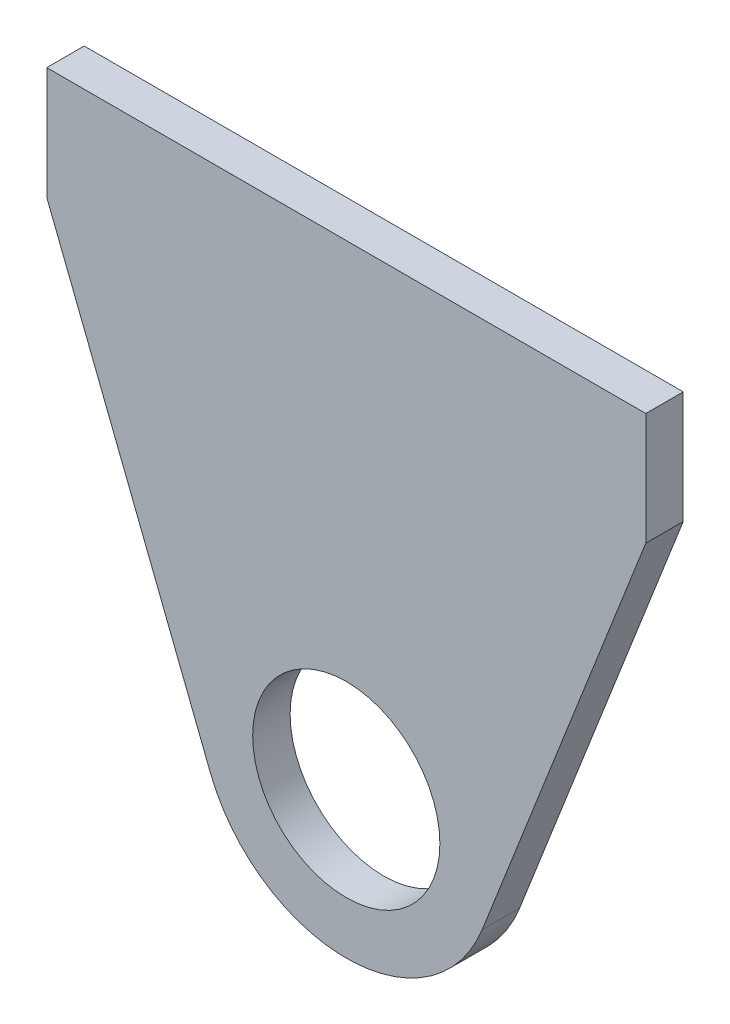
SolidWorks part; units mm, degrees
material "AISI 1020"
ref_plane "Спереди" through (0, 0, 0) normal (0, 0, 1) x (1, 0, 0)
ref_plane "Сверху" through (0, 0, 0) normal (0, 1, 0) x (1, 0, 0)
ref_plane "Справа" through (0, 0, 0) normal (1, 0, 0) x (0, 0, -1)
sketch "Эскиз2" plane through (0, 0, 0) normal (0, 0, 1) x (1, 0, 0)
  line L0 (0, -1065) -> (0, 48935) construction
  line L1 (-18.1501, -72.129) -> (-40, -16.5)
  line L2 (18.1501, -72.129) -> (40, -16.5)
  line L3 (-40, -16.5) -> (-40, -1.5)
  line L4 (-1450, -1.5) -> (100, -1.5) construction
  line L5 (40, -16.5) -> (40, -1.5)
  line L6 (-40, -1.5) -> (40, -1.5)
  circle A0 centre (0, -65) radius 12.5 construction
  circle A1 centre (0, -65) radius 12.5
  arc A2 (-18.1501, -72.129) -> (18.1501, -72.129) centre (0, -65) ccw
  point P14 (0, -1.5)
  dimension "D1" = 7
  dimension "D2" = 15
  dimension "D3" = 80
base flange "Базовая кромка1" sketch "Эскиз2" thickness 5 reverse thickness direction yes parameters "D1"=0.74
sketch "Сгиб-Линии1" [suppressed] plane through (0, 0, 0) normal (0, 1, 0) x (1, 0, 0)
sketch "Граничная рамка1" [suppressed] plane through (0, 0, 0) normal (0, 1, 0) x (1, 0, 0)
sheet metal parameters "Листовой металл3" thickness 5 parameters "D1"=0.74
flat pattern "Развертка3" [suppressed]
sketch "Сгиб-Линии2" plane through (0, 0, 0) normal (0, 1, 0) x (1, 0, 0)
sketch3d "Граничная рамка2" [suppressed]
  line L0 (-40, 63.5, 0) -> (-40, -19.5, 0) construction
  line L1 (40, 63.5, 0) -> (40, -19.5, 0) construction
  line L2 (-40, 63.5, 0) -> (40, 63.5, 0) construction
  line L3 (-40, -19.5, 0) -> (40, -19.5, 0) construction
